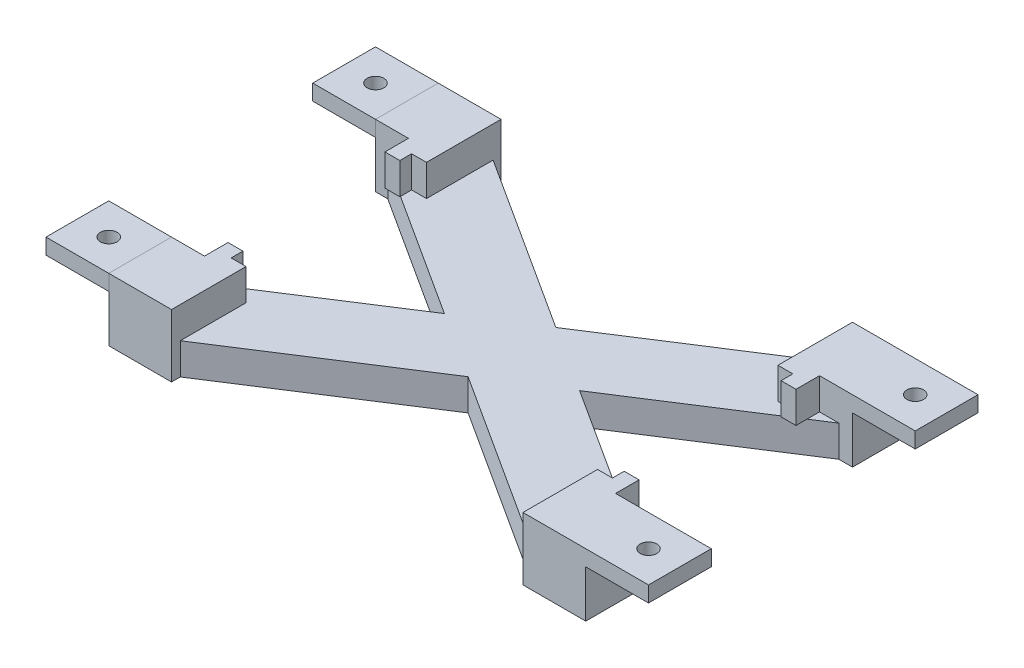
SolidWorks part; units mm, degrees
ref_plane "Front Plane" through (0, 0, 0) normal (0, 0, 1) x (1, 0, 0)
ref_plane "Top Plane" through (0, 0, 0) normal (0, 1, 0) x (1, 0, 0)
ref_plane "Right Plane" through (0, 0, 0) normal (1, 0, 0) x (0, 0, -1)
sketch "Sketch1" plane through (0, 0, 0) normal (0, 1, 0) x (1, 0, 0)
  line L0 (-66, 52.5) -> (-66, 32.5)
  line L1 (-66, -42.5) -> (66, -42.5) construction
  line L2 (-66, -42.5) -> (-66, 42.5) construction
  line L3 (-66, 42.5) -> (66, 42.5) construction
  line L4 (66, -42.5) -> (66, 42.5) construction
  line L5 (-66, -42.5) -> (66, 42.5) construction
  line L6 (-66, 42.5) -> (66, -42.5) construction
  line L7 (-76, 32.5) -> (-56, 32.5)
  line L8 (-76, 32.5) -> (-76, 52.5)
  line L9 (-76, 52.5) -> (-56, 52.5)
  line L10 (-56, 32.5) -> (-56, 52.5)
  line L11 (-76, 32.5) -> (-56, 52.5) construction
  line L12 (-76, 52.5) -> (-56, 32.5) construction
  line L13 (-76, 42.5) -> (-56, 42.5)
  line L14 (-66, -32.5) -> (-66, -52.5)
  line L15 (-76, -32.5) -> (-56, -32.5)
  line L16 (-76, -32.5) -> (-76, -52.5)
  line L17 (-76, -52.5) -> (-56, -52.5)
  line L18 (-56, -32.5) -> (-56, -52.5)
  line L19 (-76, -32.5) -> (-56, -52.5) construction
  line L20 (-76, -52.5) -> (-56, -32.5) construction
  line L21 (-76, -42.5) -> (-56, -42.5)
  line L22 (0, 0) -> (0, 42.5) construction
  line L23 (76, -42.5) -> (56, -42.5)
  line L24 (66, -32.5) -> (66, -52.5)
  line L25 (76, -52.5) -> (56, -52.5)
  line L26 (56, -32.5) -> (56, -52.5)
  line L27 (76, -32.5) -> (56, -32.5)
  line L28 (76, -32.5) -> (76, -52.5)
  line L29 (66, 52.5) -> (66, 32.5)
  line L30 (76, 42.5) -> (56, 42.5)
  line L31 (76, 52.5) -> (56, 52.5)
  line L32 (56, 32.5) -> (56, 52.5)
  line L33 (76, 32.5) -> (56, 32.5)
  line L34 (76, 32.5) -> (76, 52.5)
  point P0 (0, 0)
  dimension "D1" = 132
  dimension "D2" = 85
  dimension "D3" = 20
  dimension "D4" = 20
  dimension "D5" = 20
  dimension "D6" = 20
extrude "Boss-Extrude1" add sketch "Sketch1" along normal blind 10 contours L16 L21 L14 L15 | L21 L16 L17 L14 | L21 L14 L17 L18 | L13 L8 L7 L0 | L8 L13 L0 L9 | L0 L13 L10 L9 | L32 L30 L29 L31 | L30 L34 L31 L29 | L33 L34 L30 L29 | L23 L26 L25 L24 | L28 L23 L24 L25 | L28 L27 L24 L23 | L13 L0 L7 L10 | L24 L27 L26 L23 | L14 L21 L18 L15 | L33 L29 L30 L32 region at (-61, 0, -47.5) region at (-71, 0, -47.5) region at (-61, 0, -37.5) region at (-71, 0, -37.5) region at (-61, 0, 37.5) region at (-71, 0, 37.5) region at (-61, 0, 47.5) region at (-71, 0, 47.5) region at (71, 0, 47.5) region at (71, 0, 37.5) region at (61, 0, 47.5) region at (61, 0, 37.5) region at (71, 0, -47.5) region at (61, 0, -47.5) region at (71, 0, -37.5) region at (61, 0, -37.5)
extrude "Boss-Extrude2" add sketch "Sketch1<3>" against normal blind 10 contours L21 L16 L17 L14 | L14 L21 L18 L15 | L21 L14 L17 L18 | L16 L21 L14 L15 | L28 L23 L24 L25 | L28 L27 L24 L23 | L23 L26 L25 L24 | L24 L27 L26 L23 | L33 L34 L30 L29 | L30 L34 L31 L29 | L32 L30 L29 L31 | L33 L29 L30 L32 | L0 L13 L10 L9 | L13 L0 L7 L10 | L13 L8 L7 L0 | L8 L13 L0 L9 region at (-61, 0, -47.5) region at (-71, 0, -47.5) region at (-61, 0, -37.5) region at (-71, 0, -37.5) region at (-61, 0, 37.5) region at (-71, 0, 37.5) region at (-61, 0, 47.5) region at (-71, 0, 47.5) region at (71, 0, 47.5) region at (71, 0, 37.5) region at (61, 0, 47.5) region at (61, 0, 37.5) region at (71, 0, -47.5) region at (61, 0, -47.5) region at (71, 0, -37.5) region at (61, 0, -37.5)
sketch "Sketch1<3>" plane through (0, 0, 0) normal (0, 1, 0) x (1, 0, 0) same geometry as "Sketch1"
sketch "Sketch2" plane through (0, 0, 0) normal (0, 1, 0) x (1, 0, 0)
  line L0 (-72.3356, 32.6611) -> (59.6644, -52.3389)
  line L1 (-72.3356, 32.6611) -> (-59.6644, 52.3389)
  line L2 (59.6644, -52.3389) -> (72.3356, -32.6611)
  line L3 (-59.6644, 52.3389) -> (72.3356, -32.6611)
  line L4 (-72.3356, 32.6611) -> (72.3356, -32.6611) construction
  line L5 (59.6644, -52.3389) -> (-59.6644, 52.3389) construction
  line L6 (72.2153, 32.848) -> (-59.7847, -52.152)
  line L7 (72.2153, 32.848) -> (59.7847, 52.152)
  line L8 (-59.7847, -52.152) -> (-72.2153, -32.848)
  line L9 (59.7847, 52.152) -> (-72.2153, -32.848)
  line L10 (72.2153, 32.848) -> (-72.2153, -32.848) construction
  line L11 (-59.7847, -52.152) -> (59.7847, 52.152) construction
  point P1 (0, 0)
  point P2 (0, 0)
extrude "Boss-Extrude3" add sketch "Sketch2" against normal blind 10 contours L9 L3 L1 L0 | L3 L9 L0 L6 | L7 L9 L3 L6 | L3 L6 L0 L2 | L0 L9 L8 L6 region at (-38.0704, 0, -24.8896) region at (0, 0, 0) region at (-38.1809, 0, 24.948) region at (38.0704, 0, 24.8896) region at (38.1809, 0, -24.948)
sketch "Sketch3" plane through (-76, 0, 0) normal (-1, 0, 0) x (0, 0, 1)
  line L0 (-32.5, 10) -> (-32.5, -10) construction
  line L1 (-52.5, 10) -> (-32.5, 10)
  line L2 (-52.5, 10) -> (-52.5, 5)
  line L3 (-52.5, 5) -> (-32.5, 5)
  line L4 (-32.5, 10) -> (-32.5, 5)
  line L5 (52.5, 10) -> (52.5, -10) construction
  line L6 (32.5, 10) -> (52.5, 10)
  line L7 (32.5, 10) -> (32.5, 5)
  line L8 (32.5, 5) -> (52.5, 5)
  line L9 (52.5, 10) -> (52.5, 5)
  dimension "D1" = 5
extrude "Boss-Extrude4" add sketch "Sketch3" along normal blind 20
sketch "Sketch8" plane through (0, 0, 0) normal (0, 1, 0) x (1, 0, 0)
  line L0 (-76, -32.5) -> (-56, -32.5) construction
  line L1 (-60.75, -28.75) -> (60.75, -28.75) construction
  line L2 (-60.75, -28.75) -> (-60.75, 28.75) construction
  line L3 (-60.75, 28.75) -> (60.75, 28.75) construction
  line L4 (60.75, -28.75) -> (60.75, 28.75) construction
  line L5 (-60.75, -28.75) -> (60.75, 28.75) construction
  line L6 (-60.75, 28.75) -> (60.75, -28.75) construction
  line L7 (-65.5, 25) -> (-56, 25)
  line L8 (-65.5, 25) -> (-65.5, 32.5)
  line L9 (-65.5, 32.5) -> (-56, 32.5)
  line L10 (-56, 25) -> (-56, 32.5)
  line L11 (-56, -32.5) -> (-56, -52.5) construction
  line L12 (-76, 32.5) -> (-56, 32.5) construction
  line L13 (65.5, 25) -> (56, 25)
  line L14 (65.5, 25) -> (65.5, 32.5)
  line L15 (65.5, 32.5) -> (56, 32.5)
  line L16 (56, 25) -> (56, 32.5)
  line L17 (76, 32.5) -> (56, 32.5) construction
  line L18 (56, 32.5) -> (56, 52.5) construction
  line L19 (65.5, -25) -> (56, -25)
  line L20 (65.5, -25) -> (65.5, -32.5)
  line L21 (65.5, -32.5) -> (56, -32.5)
  line L22 (56, -25) -> (56, -32.5)
  line L23 (56, -32.5) -> (56, -52.5) construction
  line L24 (76, -32.5) -> (56, -32.5) construction
  line L25 (-65.5, -25) -> (-56, -25)
  line L26 (-65.5, -25) -> (-65.5, -32.5)
  line L27 (-65.5, -32.5) -> (-56, -32.5)
  line L28 (-56, -25) -> (-56, -32.5)
  line L31 (-60.75, -25) -> (-60.75, -28.75)
  line L32 (-60.75, -28.75) -> (-56, -28.75)
  line L33 (56, -28.75) -> (60.75, -28.75)
  line L34 (60.75, -28.75) -> (60.75, -25)
  line L35 (56, 28.75) -> (60.75, 28.75)
  line L36 (60.75, 28.75) -> (60.75, 25)
  line L37 (-56, 28.75) -> (-60.75, 28.75)
  line L38 (-60.75, 28.75) -> (-60.75, 25)
  line L39 (-56, 32.5) -> (-56, 52.5) construction
  point P0 (0, 0)
  dimension "D1" = 121.5
  dimension "D2" = 57.5
extrude "Boss-Extrude6" add sketch "Sketch8" along normal blind 10 contours L38 L37 L10 L9 L8 L7 | L32 L31 L25 L26 L27 L28 | L34 L33 L22 L21 L20 L19 | L35 L36 L13 L14 L15 L16 region at (-61.5417, 0, -29.375) region at (61.5417, 0, -29.375) region at (61.5417, 0, 29.375) region at (-61.5417, 0, 29.375)
mirror "Mirror1" about plane through (0, 0, 0) normal (1, 0, 0) of "Boss-Extrude4"
hole_wizard "#4 (0.209) Diameter Hole1" positions "3DSketch2" profile "Sketch10" hole size "#4" standard "ANSI Inch" end condition through all
sketch3d "3DSketch2"
  line L0 (-86, 10, -52.5) -> (-86, 10, -32.5) construction
  line L1 (-96, 10, -52.5) -> (-76, 10, -52.5) construction
  line L2 (-96, 10, -32.5) -> (-76, 10, -32.5) construction
  line L4 (-96, 10, -42.5) -> (-76, 10, -42.5) construction
  line L5 (-96, 10, -32.5) -> (-96, 10, -52.5) construction
  line L6 (-76, 10, -32.5) -> (-76, 10, -52.5) construction
  line L8 (-86, 10, 32.5) -> (-86, 10, 52.5) construction
  line L9 (-96, 10, 32.5) -> (-76, 10, 32.5) construction
  line L10 (-96, 10, 52.5) -> (-76, 10, 52.5) construction
  line L12 (-96, 10, 42.5) -> (-76, 10, 42.5) construction
  line L13 (-96, 10, 52.5) -> (-96, 10, 32.5) construction
  line L14 (-76, 10, 52.5) -> (-76, 10, 32.5) construction
  line L17 (86, 10, 32.5) -> (86, 10, 52.5) construction
  line L18 (96, 10, 32.5) -> (65.5, 10, 32.5) construction
  line L19 (96, 10, 52.5) -> (56, 10, 52.5) construction
  line L21 (96, 10, 42.5) -> (56, 10, 42.5) construction
  line L22 (96, 10, 52.5) -> (96, 10, 32.5) construction
  line L23 (56, 10, 28.75) -> (56, 10, 52.5) construction
  line L25 (86, 10, -52.5) -> (86, 10, -32.5) construction
  line L26 (96, 10, -52.5) -> (56, 10, -52.5) construction
  line L27 (96, 10, -32.5) -> (65.5, 10, -32.5) construction
  line L29 (96, 10, -42.5) -> (56, 10, -42.5) construction
  line L30 (96, 10, -32.5) -> (96, 10, -52.5) construction
  line L31 (56, 10, -28.75) -> (56, 10, -52.5) construction
  point P0 (-86, 10, -42.5)
  point P2 (86, 10, -42.5)
  point P4 (86, 10, 42.5)
  point P6 (-86, 10, 42.5)
  dimension "D1" = 10
  dimension "D2" = 10
sketch "Sketch10" plane through (-86, 10, -42.5) normal (1, 0, 0) x (0, 0, 1)
  line L0 (0, 0) -> (0, 20)
  line L1 (0, 20) -> (2.6543, 20)
  line L2 (2.6543, 20) -> (2.6543, 0)
  line L5 (2.6543, 0) -> (0, 0)
  line L11 (0, -6.35) -> (0, 107.95) construction
  dimension "Thru Hole Dia." = 5.3086
  dimension "Thru Hole Depth" = 20
